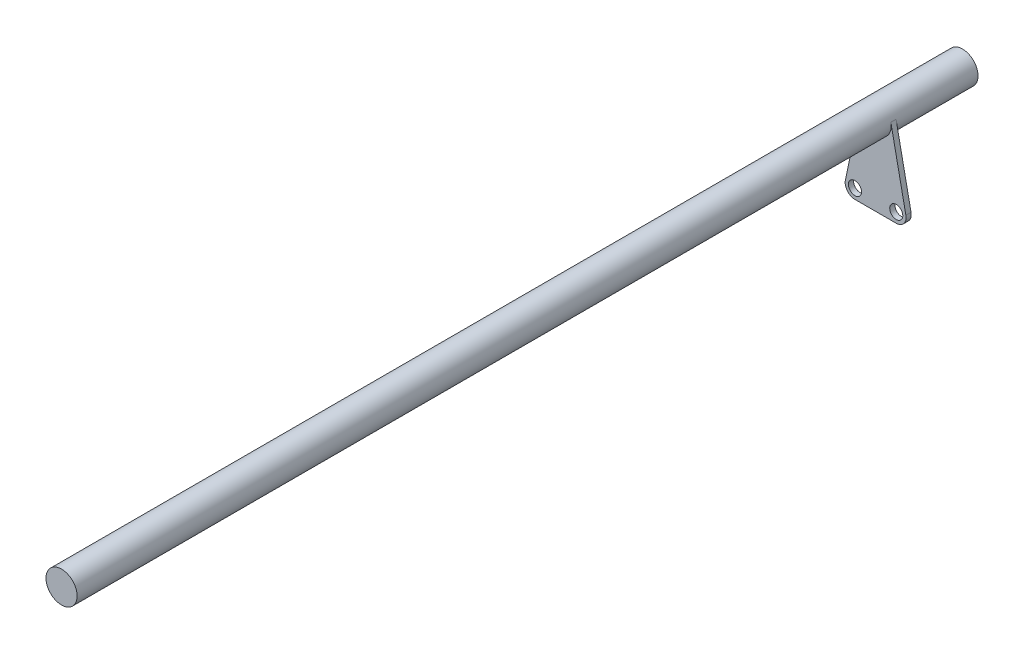
SolidWorks part; units mm, degrees
ref_plane "Front Plane" through (0, 0, 0) normal (0, 0, 1) x (1, 0, 0)
ref_plane "Top Plane" through (0, 0, 0) normal (0, 1, 0) x (1, 0, 0)
ref_plane "Right Plane" through (0, 0, 0) normal (1, 0, 0) x (0, 0, -1)
sketch "Sketch1" plane through (0, 0, 0) normal (0, 0, 1) x (1, 0, 0)
  circle A0 centre (0, 0) radius 9.525
  dimension "D1" = 19.05
extrude "Boss-Extrude1" add sketch "Sketch1" along normal mid plane 500
sketch "Sketch2" plane through (0, 0, -250) normal (0, 0, -1) x (-1, 0, 0)
  line L0 (-9.33, 1.9175) -> (-18.5187, -42.7921)
  line L3 (-12.6415, -50) -> (12.6415, -50)
  line L4 (18.5187, -42.7921) -> (9.33, 1.9175)
  circle A3 centre (0, 0) radius 9.525 construction
  arc A4 (9.33, 1.9175) -> (-9.33, 1.9175) centre (0, 0) ccw
  arc A5 (12.6415, -50) -> (18.5187, -42.7921) centre (12.6415, -44) ccw
  arc A6 (-18.5187, -42.7921) -> (-12.6415, -50) centre (-12.6415, -44) ccw
  point P9 (0, -50)
  point P13 (20, -50)
  point P16 (-20, -50)
  dimension "D1" = 50
  dimension "D3" = 6
  dimension "D2" = 40
extrude "Boss-Extrude2" add sketch "Sketch2" along normal mid plane 3.175
sketch "Sketch3" plane through (0, 0, -248.4125) normal (0, 0, 1) x (1, 0, 0)
  circle A2 centre (-12.6415, -44) radius 4
  circle A3 centre (12.6415, -44) radius 4
  arc A4 (-18.5187, -42.7921) -> (-12.6415, -50) centre (-12.6415, -44) ccw construction
  arc A5 (12.6415, -50) -> (18.5187, -42.7921) centre (12.6415, -44) ccw construction
  dimension "D1" = 8
  dimension "D2" = 8
extrude "Cut-Extrude1" cut sketch "Sketch3" against normal up to next
sketch "Sketch4" plane through (0, 0, -251.5875) normal (0, 0, -1) x (-1, 0, 0)
  circle A0 centre (0, 0) radius 9.525
  arc A1 (9.33, 1.9175) -> (-9.33, 1.9175) centre (0, 0) ccw construction
extrude "Boss-Extrude3" add sketch "Sketch4" along normal blind 50 contours A0
